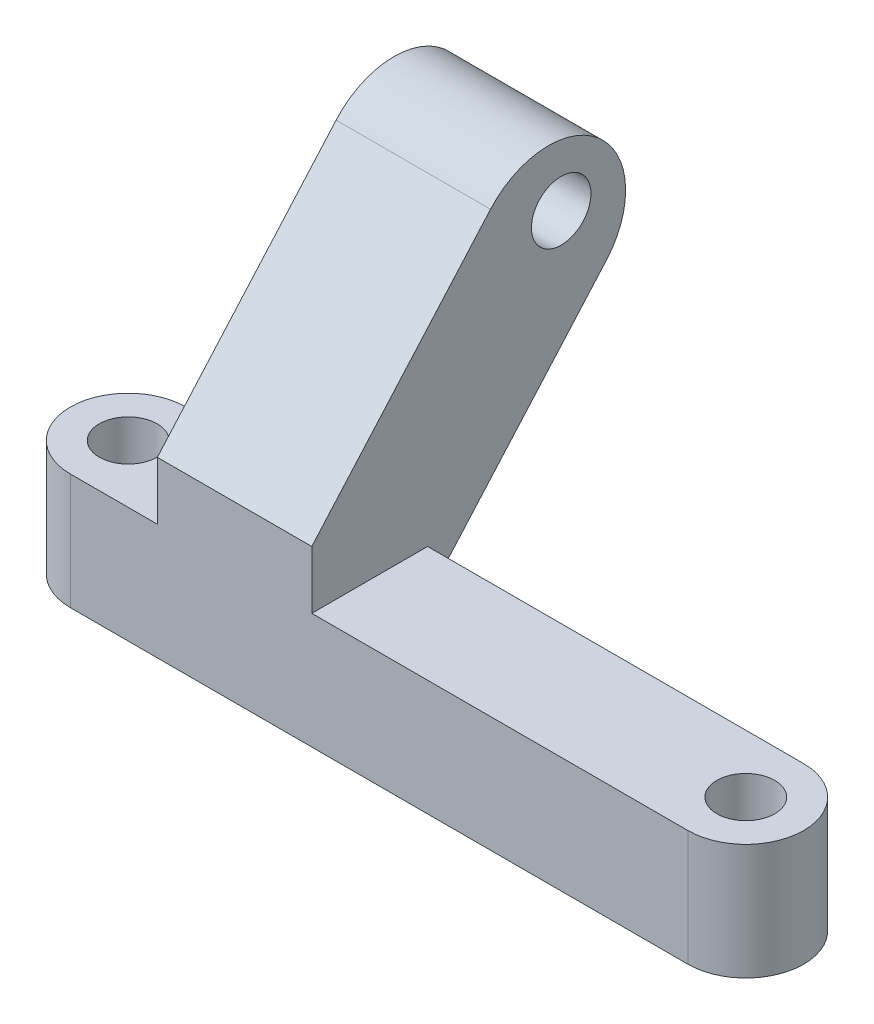
SolidWorks part; units mm, degrees
ref_plane "前基準面" through (0, 0, 0) normal (0, 0, 1) x (1, 0, 0)
ref_plane "上基準面" through (0, 0, 0) normal (0, 1, 0) x (1, 0, 0)
ref_plane "右基準面" through (0, 0, 0) normal (1, 0, 0) x (0, 0, -1)
sketch "草圖1" plane through (0, 0, 0) normal (0, 1, 0) x (1, 0, 0)
  line L0 (-38.677, 0) -> (-6.677, 0) construction
  line L1 (-38.677, 3) -> (-6.677, 3)
  line L2 (-38.677, -3) -> (-6.677, -3)
  line L4 (-34.1647, 3) -> (-26.1647, 3)
  line L5 (-34.1647, 3) -> (-34.1647, -3)
  line L6 (-34.1647, -3) -> (-26.1647, -3)
  line L7 (-26.1647, 3) -> (-26.1647, -3)
  arc A0 (-38.677, 3) -> (-38.677, -3) centre (-38.677, 0) ccw
  arc A1 (-6.677, -3) -> (-6.677, 3) centre (-6.677, 0) ccw
  circle A2 centre (-6.677, 0) radius 1.5
  circle A3 centre (-38.677, 0) radius 1.5
  point P3 (-22.677, 0)
  dimension "D1" = 32
  dimension "D2" = 8
  dimension "D4" = 3
  dimension "D3" = 6
extrude "填料-伸長2" add sketch "草圖1" against normal blind 6 contours A3 L5 L1 A0 L2 | L5 L0 L7 L1 | L0 L5 L2 L7 | L2 A1 L1 L7 A2 region at (-34.2608, 0, 1.5) region at (-30.1647, 0, -1.5) region at (-30.1647, 0, 1.5) region at (-25.9319, 0, -1.5)
extrude "填料-伸長3" add sketch "草圖1<4>" along normal blind 3 contours L0 L5 L2 L7 | L5 L0 L7 L1 region at (-30.1647, 0, -1.5) region at (-30.1647, 0, 1.5)
sketch "草圖1<4>" plane through (0, 0, 0) normal (0, 1, 0) x (1, 0, 0) same geometry as "草圖1"
sketch "草圖3" plane through (-26.1647, 0, 0) normal (1, 0, 0) x (0, 0, -1)
  line L0 (-3, 3) -> (-3, 0) construction
  line L2 (-3, 2.6558) -> (-3, 0)
  line L3 (9.2601, 10.8542) -> (0, 0.3542) construction
  line L4 (3, -6) -> (3, 0) construction
  line L5 (12.2601, 8.2085) -> (6.2601, 13.5)
  line L6 (12.2601, 8.2085) -> (3, -2.2915)
  line L7 (6.2601, 13.5) -> (-3, 3)
  line L8 (3, -2.2915) -> (-3, 3)
  line L9 (12.2601, 8.2085) -> (3, -2.2915)
  line L10 (6.2601, 13.5) -> (-3, 3)
  arc A0 (12.2601, 8.2085) -> (6.2601, 13.5) centre (9.2601, 10.8542) ccw
  arc A1 (-3, 3) -> (3, -2.2915) centre (0, 0.3542) ccw
  point P15 (4.6301, 5.6042)
  dimension "D1" = 8
  dimension "D2" = 14
extrude "填料-伸長28" add sketch "草圖3" against normal blind 8 contours L5 A0 | L5 L7 L8 L6 region at (-26.1647, 12.1275, -10.383)
sketch "草圖8" plane through (-26.1647, 0, 0) normal (1, 0, 0) x (0, 0, -1)
  line L0 (6.2601, 13.5) -> (-3, 3) construction
  circle A0 centre (9.9216, 11.6042) radius 1.5424
  arc A1 (12.2601, 8.2085) -> (6.2601, 13.5) centre (9.2601, 10.8542) ccw construction
  point P4 (11.9059, 13.8542)
  dimension "D1" = 4
  dimension "D2" = 3
extrude "除料-伸長2" cut sketch "草圖8" against normal blind 12 contours A0
